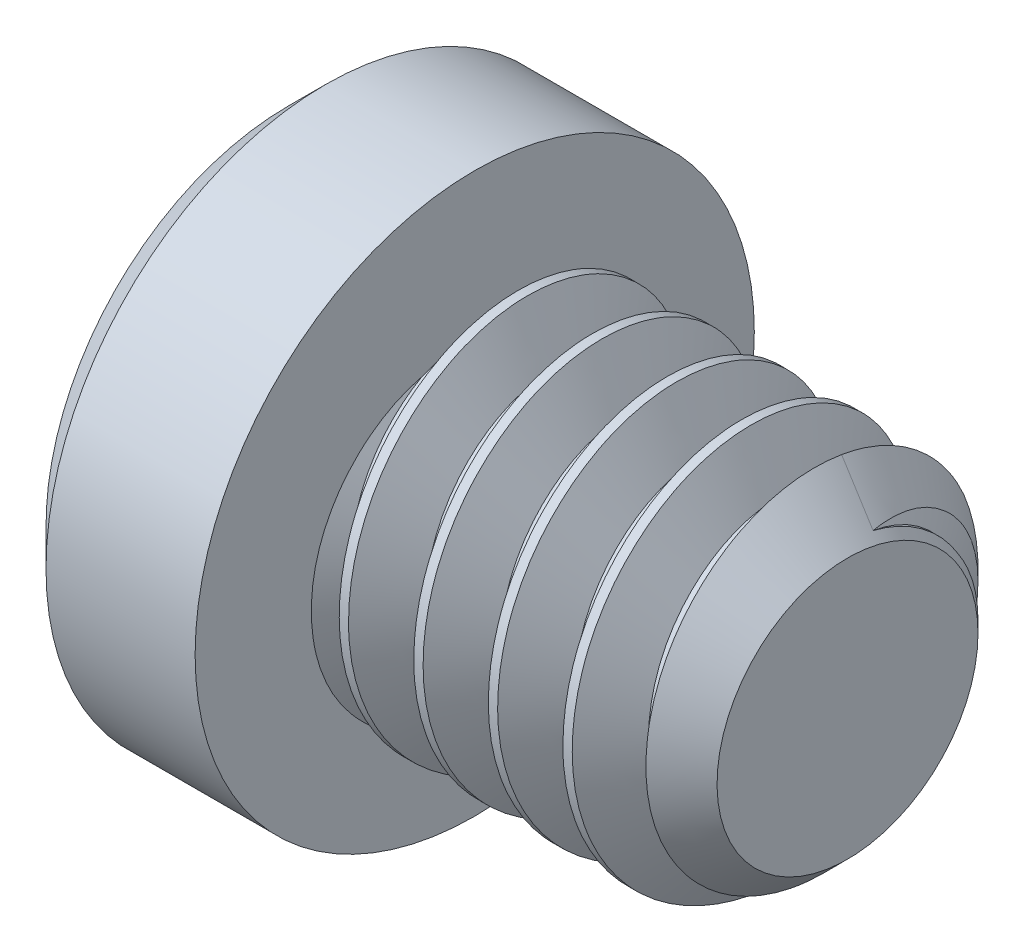
SolidWorks part; units mm, degrees
ref_plane "Front Plane" through (0, 0, 0) normal (0, 0, 1) x (1, 0, 0)
ref_plane "Top Plane" through (0, 0, 0) normal (0, 1, 0) x (1, 0, 0)
ref_plane "Right Plane" through (0, 0, 0) normal (1, 0, 0) x (0, 0, -1)
sketch "Sketch1" plane through (0, 0, 0) normal (0, 0, 1) x (1, 0, 0)
  line L0 (3.175, 0) -> (-3.175, 0) construction
  line L1 (3.175, 3.175) -> (3.175, -3.175) construction
  line L2 (-3.175, 4.7625) -> (-3.175, -4.7625) construction
  line L3 (-3.175, 4.7625) -> (-5.715, 4.7625) construction
  line L4 (-5.715, 4.7625) -> (-6.35, 4.1275) construction
  line L5 (-6.35, 4.1275) -> (-6.35, -4.1275) construction
  line L6 (-6.35, -4.1275) -> (-5.715, -4.7625) construction
  line L7 (-5.715, -4.7625) -> (-3.175, -4.7625) construction
  point P7 (-3.9624, 0)
  point P12 (-1.905, -3.175)
  dimension "D1" = 45
  dimension "D2" = 5.08
  dimension "Dec." = 6.35
  dimension "Length" = 6.35
  dimension "Head Dia" = 9.525
  dimension "Head Height" = 3.175
  dimension "Hex Depth" = 2.3876
  dimension "Chamfer" = 0.635
ref_plane "Plane1" through (3.175, 0, 0) normal (1, 0, 0) x (0, 0, -1)
ref_plane "Plane2" through (-6.35, 0, 0) normal (1, 0, 0) x (0, 0, -1)
sketch "Sketch2" plane through (3.175, 0, 0) normal (1, 0, 0) x (0, 0, -1)
  circle A0 centre (0, 0) radius 3.175
extrude "Boss-Extrude1" add sketch "Sketch2" against normal up to vertex (6.35 mm away) up to point (-3.175, 0, 0)
sketch "Sketch3" plane through (3.175, 0, 0) normal (1, 0, 0) x (0, 0, -1)
  circle A0 centre (0, 0) radius 3.175 construction
  circle A1 centre (0, 0) radius 3.175
curve "Helix/Spiral1" pitch 1.27 height 7.62 radius 3.175 centre (3.175, 0, 0) axis (-1, 0, 0) start towards (0, 1, 0) parameters "Pitch"=1.27
chamfer "Chamfer1" distance 0.9525 angle 45 1 edges at (3.175, 0, -3.175)
sketch "Sketch5" plane through (0, 0, 0) normal (0, 0, 1) x (1, 0, 0)
  line L0 (2.6194, 3.175) -> (3.7306, 3.175)
  line L1 (3.7306, 3.175) -> (3.2544, 2.3501)
  line L2 (3.2544, 2.3501) -> (3.0956, 2.3501)
  line L3 (3.0956, 2.3501) -> (2.6194, 3.175)
  line L4 (3.175, 2.3501) -> (3.175, 3.175) construction
  line L5 (2.8575, 2.7626) -> (3.4925, 2.7626) construction
  dimension "D1" = 60
  dimension "D2" = 0.635
  dimension "D3" = 0.1588
sweep "Cut-Sweep1" cut profiles "Sketch5" path "Helix/Spiral1"
sketch "Sketch4" plane through (-6.35, 0, 0) normal (1, 0, 0) x (0, 0, -1)
  line L0 (-4.7625, 0.7937) -> (4.7625, 0.7937) construction
  line L1 (0, 1.8331) -> (-1.5875, 0.9165)
  line L2 (-1.5875, 0.9165) -> (-1.5875, -0.9165)
  line L3 (-1.5875, -0.9165) -> (0, -1.8331)
  line L4 (0, -1.8331) -> (1.5875, -0.9165)
  line L5 (1.5875, -0.9165) -> (1.5875, 0.9165)
  line L6 (1.5875, 0.9165) -> (0, 1.8331)
  line L7 (0, 0) -> (0, 0.7937) construction
  circle A0 centre (0, 0) radius 1.5875 construction
  dimension "D1" = 9.525
  dimension "Hex Size" = 3.175
  dimension "D2" = 0.7937
sketch "Sketch6" plane through (0, 0, 0) normal (0, 0, 1) x (1, 0, 0)
  line L0 (-5.715, 4.7625) -> (-6.35, 4.1275) construction
  line L1 (-3.175, 4.7625) -> (-5.715, 4.7625) construction
  line L2 (-3.175, 4.7625) -> (-3.175, -4.7625) construction
  line L3 (-6.35, 4.1275) -> (-6.35, -4.1275) construction
  line L4 (-5.715, 4.7625) -> (-6.35, 4.1275)
  line L5 (-3.175, 4.7625) -> (-5.715, 4.7625)
  line L6 (-3.175, 4.7625) -> (-3.175, 0)
  line L7 (-6.35, 4.1275) -> (-6.35, 0)
  line L8 (-3.175, 0) -> (-6.35, 0) construction
  line L9 (-3.175, 0) -> (-6.35, 0)
revolve "Revolve1" add sketch "Sketch6" angle 360 about L8
extrude "Cut-Extrude1" cut sketch "Sketch4" along normal up to vertex (2.3876 mm away) up to point (-3.9624, 0, 0)
sketch "Sketch8" plane through (-6.35, 0, 0) normal (-1, 0, 0) x (0, 0, 1)
  circle A1 centre (0, 0) radius 1.8331
extrude "Cut-Extrude2" cut sketch "Sketch8" against normal through all draft 45
equation "\"D3@Helix/Spiral1\" = \"Length@Sketch1\"+\"Pitch@Helix/Spiral1\""
equation "\"D3@Sketch5\" = \"Pitch@Helix/Spiral1\"*.125"
equation "\"D2@Sketch5\" = \"Pitch@Helix/Spiral1\"*.50"
equation "\"D1@Chamfer1\" = \"Pitch@Helix/Spiral1\"*.75"
equation "\"D2@Sketch1\" = \"Pitch@Helix/Spiral1\"*4"
equation "\"D1@Sketch4\" = \"Head Dia@Sketch1\""
